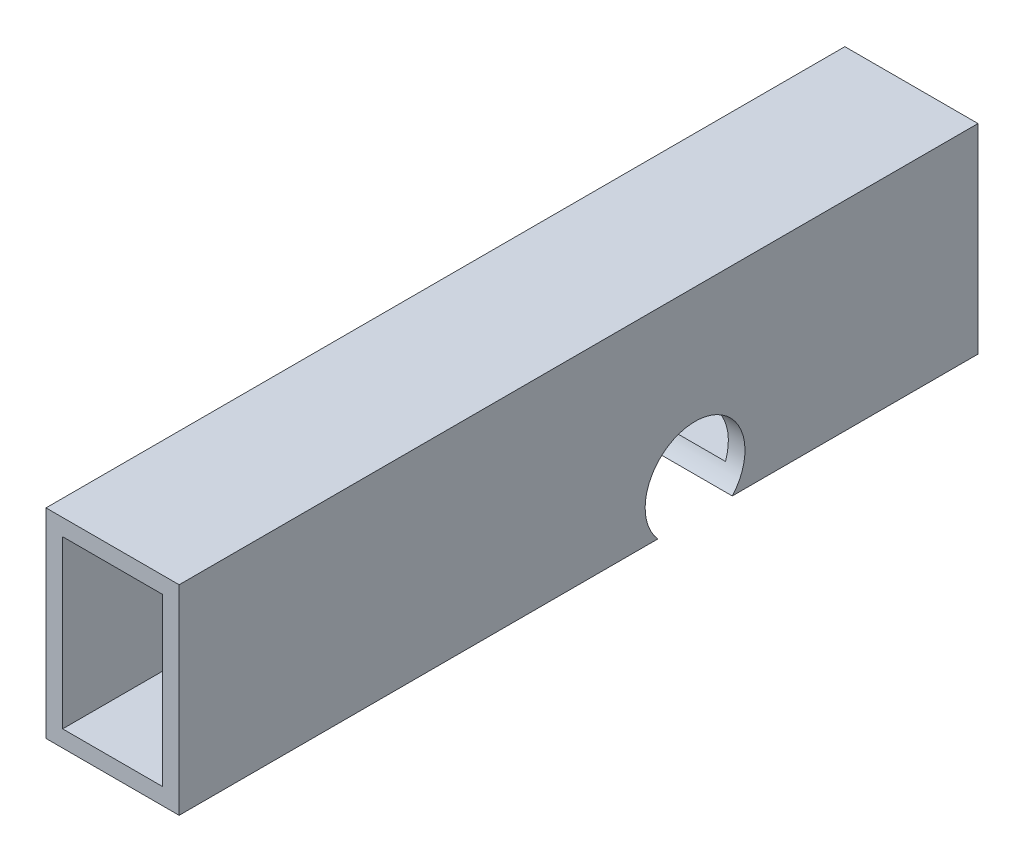
SolidWorks part; units mm, degrees
ref_plane "Front Plane" through (0, 0, 0) normal (0, 0, 1) x (1, 0, 0)
ref_plane "Top Plane" through (0, 0, 0) normal (0, 1, 0) x (1, 0, 0)
ref_plane "Right Plane" through (0, 0, 0) normal (1, 0, 0) x (0, 0, -1)
sketch "Sketch1" plane through (0, 0, 0) normal (0, 0, 1) x (1, 0, 0)
  line L1 (-12.7, 19.05) -> (12.7, 19.05)
  line L2 (-12.7, 19.05) -> (-12.7, -19.05)
  line L3 (-12.7, -19.05) -> (12.7, -19.05)
  line L4 (12.7, 19.05) -> (12.7, -19.05)
  line L5 (-12.7, 19.05) -> (12.7, -19.05) construction
  line L6 (-12.7, -19.05) -> (12.7, 19.05) construction
  point P0 (0, 0)
  dimension "D1" = 25.4
  dimension "D2" = 38.1
extrude "Boss-Extrude1" add sketch "Sketch1" along normal blind 152.4
shell "Shell1" thickness 3.175 removed face at (0, 0, 0) removed face at (0, 0, 152.4)
sketch "Sketch2" plane through (12.7, 0, 0) normal (1, 0, 0) x (0, 0, -1)
  line L0 (-152.4, -19.05) -> (0, -19.05) construction
  line L1 (0, -19.05) -> (0, 19.05) construction
  circle A0 centre (-53.975, -12.7) radius 9.525
  point P2 (-50.8, 0)
  dimension "D1" = 19.05
  dimension "D2" = 6.35
  dimension "D3" = 53.975
extrude "Cut-Extrude1" cut sketch "Sketch2" against normal through all
